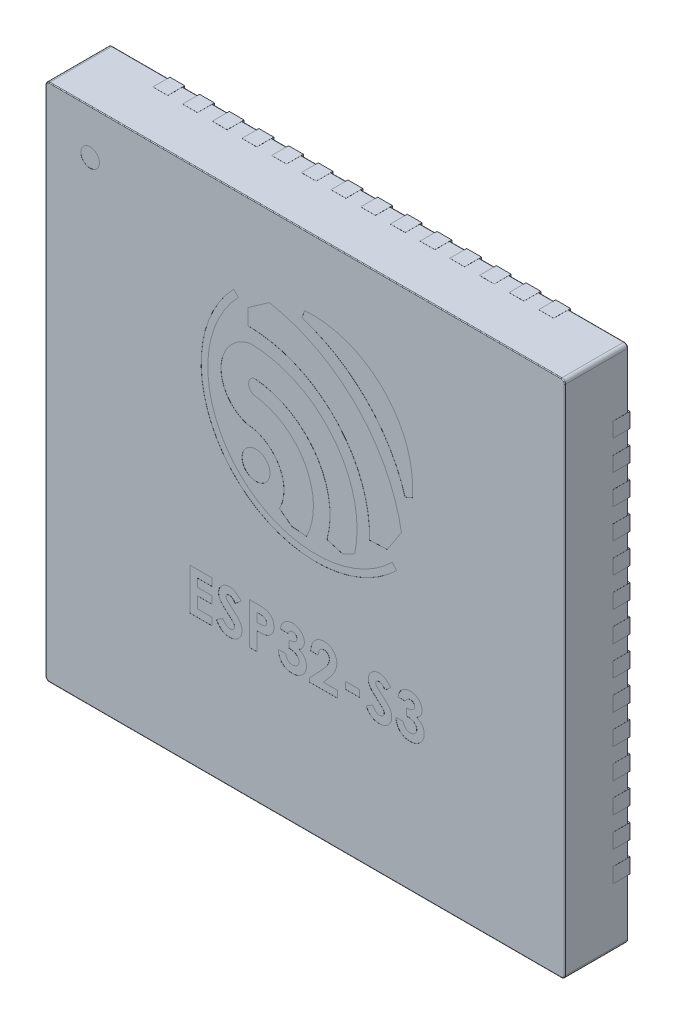
SolidWorks part; units mm, degrees
other "ESP32-S3-SoC" parameters "D5"=0.3678, "D1"=3.1308, "D2"=3.0402, "D3"=0.4115, "D4"=0.3, "D6"=0.3296, "D7"=0.2637, "D8"=0.9806, "D10"=0.4, "D11"=0.25, "D9"=7
ref_plane "Front Plane" through (0, 0, 0) normal (0, 0, 1) x (1, 0, 0)
ref_plane "Top Plane" through (0, 0, 0) normal (0, 1, 0) x (1, 0, 0)
ref_plane "Right Plane" through (0, 0, 0) normal (1, 0, 0) x (0, 0, -1)
sketch "Sketch1" plane through (0, 0, 0) normal (0, 1, 0) x (1, 0, 0)
  line L1 (-3.5, -3.5) -> (3.5, -3.5)
  line L2 (-3.5, -3.5) -> (-3.5, 3.5)
  line L3 (-3.5, 3.5) -> (3.5, 3.5)
  line L4 (3.5, -3.5) -> (3.5, 3.5)
  line L5 (-3.5, -3.5) -> (3.5, 3.5) construction
  line L6 (-3.5, 3.5) -> (3.5, -3.5) construction
  point P0 (0, 0)
  dimension "D1" = 7
  dimension "D2" = 7
extrude "Boss-Extrude1" add sketch "Sketch1" along normal blind 0.85
fillet "Fillet1" radius 0.05 4 edges at (3.5, 0.425, -3.5) (3.5, 0.425, 3.5) (-3.5, 0.425, 3.5) (-3.5, 0.425, -3.5)
fillet "Fillet2" radius 0.01 16 edges at (3.4854, 0.85, 3.4854) (0, 0.85, 3.5) (-3.4854, 0.85, 3.4854) (-3.5, 0.85, 0) (-3.4854, 0.85, -3.4854) (0, 0.85, -3.5) (3.4854, 0.85, -3.4854) (3.5, 0.85, 0) (3.5, 0, 0) (3.4854, 0, -3.4854) (0, 0, -3.5) (3.4854, 0, 3.4854) (0, 0, 3.5) (-3.4854, 0, 3.4854) (-3.5, 0, 0) (-3.4854, 0, -3.4854)
sketch "Sketch2" plane through (0, 0, 0) normal (0, -1, 0) x (1, 0, 0)
  line L0 (1.5, 2) -> (2, 1.5)
  line L1 (-1.875, -2) -> (1.875, -2)
  line L2 (-2, -1.875) -> (-2, 1.875)
  line L3 (-1.875, 2) -> (1.5, 2)
  line L4 (2, -1.875) -> (2, 1.5)
  line L5 (-1.9634, -1.9634) -> (2, 2) construction
  line L6 (-1.9634, 1.9634) -> (1.9634, -1.9634) construction
  line L7 (1.5, 2) -> (2, 2) construction
  line L8 (2, 1.5) -> (2, 2) construction
  line L9 (-2, 2) -> (-1.875, 2) construction
  line L10 (-2, 2) -> (-1.9634, 1.9634) construction
  line L11 (-2, 1.875) -> (-2, 2) construction
  line L12 (-2, -2) -> (-2, -1.875) construction
  line L13 (-2, -2) -> (-1.9634, -1.9634) construction
  line L14 (-2, -2) -> (-1.875, -2) construction
  line L15 (2, -2) -> (2, -1.875) construction
  line L16 (1.9634, -1.9634) -> (2, -2) construction
  line L17 (1.875, -2) -> (2, -2) construction
  line L18 (-1.9, 3.501) -> (-1.9, 3.101)
  line L23 (-0.3, 3.501) -> (-0.1, 3.501)
  line L24 (-0.3, 3.501) -> (-0.3, 3.101)
  line L25 (-0.3, 3.101) -> (-0.1, 3.101)
  line L26 (-0.1, 3.501) -> (-0.1, 3.101)
  line L27 (-0.3, 3.501) -> (-0.1, 3.101) construction
  line L28 (-0.3, 3.101) -> (-0.1, 3.501) construction
  line L30 (-0.7, 3.501) -> (-0.7, 3.101)
  line L31 (-0.7, 3.501) -> (-0.5, 3.501)
  line L32 (-0.5, 3.501) -> (-0.5, 3.101)
  line L33 (-0.7, 3.101) -> (-0.5, 3.101)
  line L34 (-0.7, 3.101) -> (-0.5, 3.501) construction
  line L35 (-0.7, 3.501) -> (-0.5, 3.101) construction
  line L36 (-1.1, 3.501) -> (-1.1, 3.101)
  line L37 (-1.1, 3.501) -> (-0.9, 3.501)
  line L38 (-0.9, 3.501) -> (-0.9, 3.101)
  line L39 (-1.1, 3.101) -> (-0.9, 3.101)
  line L40 (-1.1, 3.101) -> (-0.9, 3.501) construction
  line L41 (-1.1, 3.501) -> (-0.9, 3.101) construction
  line L42 (-1.5, 3.501) -> (-1.5, 3.101)
  line L43 (-1.5, 3.501) -> (-1.3, 3.501)
  line L44 (-1.3, 3.501) -> (-1.3, 3.101)
  line L45 (-1.5, 3.101) -> (-1.3, 3.101)
  line L46 (-1.5, 3.101) -> (-1.3, 3.501) construction
  line L47 (-1.5, 3.501) -> (-1.3, 3.101) construction
  line L48 (-0.3, 3.501) -> (-0.7, 3.501) construction
  line L49 (0, 0.0183) -> (0, 4.8642) construction
  line L66 (0, -1000) -> (0, 49000) construction
  line L162 (-1.9, 3.501) -> (-1.7, 3.501)
  line L163 (-3.5, 3.5) -> (3.5, 3.5) construction
  line L164 (-1.7, 3.501) -> (-1.7, 3.101)
  line L165 (-1.9, 3.101) -> (-1.7, 3.101)
  line L166 (-1.9, 3.101) -> (-1.7, 3.501) construction
  line L167 (-1.9, 3.501) -> (-1.7, 3.101) construction
  line L168 (-2.3, 3.501) -> (-2.3, 3.101)
  line L169 (-2.3, 3.501) -> (-2.1, 3.501)
  line L170 (-2.1, 3.501) -> (-2.1, 3.101)
  line L171 (-2.3, 3.101) -> (-2.1, 3.101)
  line L172 (-2.3, 3.101) -> (-2.1, 3.501) construction
  line L173 (-2.3, 3.501) -> (-2.1, 3.101) construction
  line L174 (-2.7, 3.501) -> (-2.7, 3.101)
  line L175 (-2.7, 3.501) -> (-2.5, 3.501)
  line L176 (-2.5, 3.501) -> (-2.5, 3.101)
  line L177 (-2.7, 3.101) -> (-2.5, 3.101)
  line L178 (-2.7, 3.101) -> (-2.5, 3.501) construction
  line L179 (-2.7, 3.501) -> (-2.5, 3.101) construction
  line L180 (-1000, 0) -> (49000, 0) construction
  line L181 (2.7, 3.501) -> (2.5, 3.101) construction
  line L182 (2.7, 3.101) -> (2.5, 3.501) construction
  line L183 (2.3, 3.501) -> (2.1, 3.101) construction
  line L184 (2.3, 3.101) -> (2.1, 3.501) construction
  line L185 (1.9, 3.501) -> (1.7, 3.101) construction
  line L186 (1.9, 3.101) -> (1.7, 3.501) construction
  line L187 (0.3, 3.501) -> (0.7, 3.501) construction
  line L188 (1.5, 3.501) -> (1.3, 3.101) construction
  line L189 (1.5, 3.101) -> (1.3, 3.501) construction
  line L190 (1.1, 3.501) -> (0.9, 3.101) construction
  line L191 (1.1, 3.101) -> (0.9, 3.501) construction
  line L192 (0.7, 3.501) -> (0.5, 3.101) construction
  line L193 (0.7, 3.101) -> (0.5, 3.501) construction
  line L194 (0.3, 3.101) -> (0.1, 3.501) construction
  line L195 (0.3, 3.501) -> (0.1, 3.101) construction
  line L196 (2.7, 3.101) -> (2.5, 3.101)
  line L197 (2.5, 3.501) -> (2.5, 3.101)
  line L198 (2.7, 3.501) -> (2.5, 3.501)
  line L199 (2.7, 3.501) -> (2.7, 3.101)
  line L200 (2.3, 3.101) -> (2.1, 3.101)
  line L201 (2.1, 3.501) -> (2.1, 3.101)
  line L202 (2.3, 3.501) -> (2.1, 3.501)
  line L203 (2.3, 3.501) -> (2.3, 3.101)
  line L204 (1.9, 3.101) -> (1.7, 3.101)
  line L205 (1.7, 3.501) -> (1.7, 3.101)
  line L206 (1.9, 3.501) -> (1.7, 3.501)
  line L207 (1.5, 3.101) -> (1.3, 3.101)
  line L208 (1.3, 3.501) -> (1.3, 3.101)
  line L209 (1.5, 3.501) -> (1.3, 3.501)
  line L210 (1.5, 3.501) -> (1.5, 3.101)
  line L211 (1.1, 3.101) -> (0.9, 3.101)
  line L212 (0.9, 3.501) -> (0.9, 3.101)
  line L213 (1.1, 3.501) -> (0.9, 3.501)
  line L214 (1.1, 3.501) -> (1.1, 3.101)
  line L215 (0.7, 3.101) -> (0.5, 3.101)
  line L216 (0.5, 3.501) -> (0.5, 3.101)
  line L217 (0.7, 3.501) -> (0.5, 3.501)
  line L218 (0.7, 3.501) -> (0.7, 3.101)
  line L219 (0.1, 3.501) -> (0.1, 3.101)
  line L220 (0.3, 3.101) -> (0.1, 3.101)
  line L221 (0.3, 3.501) -> (0.3, 3.101)
  line L222 (0.3, 3.501) -> (0.1, 3.501)
  line L223 (1.9, 3.501) -> (1.9, 3.101)
  line L224 (0.3, -3.501) -> (0.1, -3.101) construction
  line L225 (0.3, -3.101) -> (0.1, -3.501) construction
  line L226 (0.7, -3.101) -> (0.5, -3.501) construction
  line L227 (0.7, -3.501) -> (0.5, -3.101) construction
  line L228 (1.1, -3.101) -> (0.9, -3.501) construction
  line L229 (1.1, -3.501) -> (0.9, -3.101) construction
  line L230 (1.5, -3.101) -> (1.3, -3.501) construction
  line L231 (1.5, -3.501) -> (1.3, -3.101) construction
  line L232 (0.3, -3.501) -> (0.7, -3.501) construction
  line L233 (1.9, -3.101) -> (1.7, -3.501) construction
  line L234 (1.9, -3.501) -> (1.7, -3.101) construction
  line L235 (2.3, -3.101) -> (2.1, -3.501) construction
  line L236 (2.3, -3.501) -> (2.1, -3.101) construction
  line L237 (2.7, -3.101) -> (2.5, -3.501) construction
  line L238 (2.7, -3.501) -> (2.5, -3.101) construction
  line L239 (-2.7, -3.501) -> (-2.5, -3.101) construction
  line L240 (-2.7, -3.101) -> (-2.5, -3.501) construction
  line L241 (-2.3, -3.501) -> (-2.1, -3.101) construction
  line L242 (-2.3, -3.101) -> (-2.1, -3.501) construction
  line L243 (-1.9, -3.501) -> (-1.7, -3.101) construction
  line L244 (-1.9, -3.101) -> (-1.7, -3.501) construction
  line L245 (-0.3, -3.501) -> (-0.7, -3.501) construction
  line L246 (-1.5, -3.501) -> (-1.3, -3.101) construction
  line L247 (-1.5, -3.101) -> (-1.3, -3.501) construction
  line L248 (-1.1, -3.501) -> (-0.9, -3.101) construction
  line L249 (-1.1, -3.101) -> (-0.9, -3.501) construction
  line L250 (-0.7, -3.501) -> (-0.5, -3.101) construction
  line L251 (-0.7, -3.101) -> (-0.5, -3.501) construction
  line L252 (-0.3, -3.101) -> (-0.1, -3.501) construction
  line L253 (-0.3, -3.501) -> (-0.1, -3.101) construction
  line L254 (1.9, -3.501) -> (1.9, -3.101)
  line L255 (0.3, -3.501) -> (0.1, -3.501)
  line L256 (0.3, -3.501) -> (0.3, -3.101)
  line L257 (0.3, -3.101) -> (0.1, -3.101)
  line L258 (0.1, -3.501) -> (0.1, -3.101)
  line L259 (0.7, -3.501) -> (0.7, -3.101)
  line L260 (0.7, -3.501) -> (0.5, -3.501)
  line L261 (0.5, -3.501) -> (0.5, -3.101)
  line L262 (0.7, -3.101) -> (0.5, -3.101)
  line L263 (1.1, -3.501) -> (1.1, -3.101)
  line L264 (1.1, -3.501) -> (0.9, -3.501)
  line L265 (0.9, -3.501) -> (0.9, -3.101)
  line L266 (1.1, -3.101) -> (0.9, -3.101)
  line L267 (1.5, -3.501) -> (1.5, -3.101)
  line L268 (1.5, -3.501) -> (1.3, -3.501)
  line L269 (1.3, -3.501) -> (1.3, -3.101)
  line L270 (1.5, -3.101) -> (1.3, -3.101)
  line L271 (1.9, -3.501) -> (1.7, -3.501)
  line L272 (1.7, -3.501) -> (1.7, -3.101)
  line L273 (1.9, -3.101) -> (1.7, -3.101)
  line L274 (2.3, -3.501) -> (2.3, -3.101)
  line L275 (2.3, -3.501) -> (2.1, -3.501)
  line L276 (2.1, -3.501) -> (2.1, -3.101)
  line L277 (2.3, -3.101) -> (2.1, -3.101)
  line L278 (2.7, -3.501) -> (2.7, -3.101)
  line L279 (2.7, -3.501) -> (2.5, -3.501)
  line L280 (2.5, -3.501) -> (2.5, -3.101)
  line L281 (2.7, -3.101) -> (2.5, -3.101)
  line L282 (-2.7, -3.101) -> (-2.5, -3.101)
  line L283 (-2.5, -3.501) -> (-2.5, -3.101)
  line L284 (-2.7, -3.501) -> (-2.5, -3.501)
  line L285 (-2.7, -3.501) -> (-2.7, -3.101)
  line L286 (-2.3, -3.101) -> (-2.1, -3.101)
  line L287 (-2.1, -3.501) -> (-2.1, -3.101)
  line L288 (-2.3, -3.501) -> (-2.1, -3.501)
  line L289 (-2.3, -3.501) -> (-2.3, -3.101)
  line L290 (-1.9, -3.101) -> (-1.7, -3.101)
  line L291 (-1.7, -3.501) -> (-1.7, -3.101)
  line L292 (-1.9, -3.501) -> (-1.7, -3.501)
  line L293 (-1.5, -3.101) -> (-1.3, -3.101)
  line L294 (-1.3, -3.501) -> (-1.3, -3.101)
  line L295 (-1.5, -3.501) -> (-1.3, -3.501)
  line L296 (-1.5, -3.501) -> (-1.5, -3.101)
  line L297 (-1.1, -3.101) -> (-0.9, -3.101)
  line L298 (-0.9, -3.501) -> (-0.9, -3.101)
  line L299 (-1.1, -3.501) -> (-0.9, -3.501)
  line L300 (-1.1, -3.501) -> (-1.1, -3.101)
  line L301 (-0.7, -3.101) -> (-0.5, -3.101)
  line L302 (-0.5, -3.501) -> (-0.5, -3.101)
  line L303 (-0.7, -3.501) -> (-0.5, -3.501)
  line L304 (-0.7, -3.501) -> (-0.7, -3.101)
  line L305 (-0.1, -3.501) -> (-0.1, -3.101)
  line L306 (-0.3, -3.101) -> (-0.1, -3.101)
  line L307 (-0.3, -3.501) -> (-0.3, -3.101)
  line L308 (-0.3, -3.501) -> (-0.1, -3.501)
  line L309 (-1.9, -3.501) -> (-1.9, -3.101)
  line L310 (3.501, 0.3) -> (3.101, 0.1) construction
  line L311 (3.101, 0.3) -> (3.501, 0.1) construction
  line L312 (3.101, 0.7) -> (3.501, 0.5) construction
  line L313 (3.501, 0.7) -> (3.101, 0.5) construction
  line L314 (3.101, 1.1) -> (3.501, 0.9) construction
  line L315 (3.501, 1.1) -> (3.101, 0.9) construction
  line L316 (3.101, 1.5) -> (3.501, 1.3) construction
  line L317 (3.501, 1.5) -> (3.101, 1.3) construction
  line L318 (3.501, 0.3) -> (3.501, 0.7) construction
  line L319 (3.101, 1.9) -> (3.501, 1.7) construction
  line L320 (3.501, 1.9) -> (3.101, 1.7) construction
  line L321 (3.101, 2.3) -> (3.501, 2.1) construction
  line L322 (3.501, 2.3) -> (3.101, 2.1) construction
  line L323 (3.101, 2.7) -> (3.501, 2.5) construction
  line L324 (3.501, 2.7) -> (3.101, 2.5) construction
  line L325 (3.501, -2.7) -> (3.101, -2.5) construction
  line L326 (3.101, -2.7) -> (3.501, -2.5) construction
  line L327 (3.501, -2.3) -> (3.101, -2.1) construction
  line L328 (3.101, -2.3) -> (3.501, -2.1) construction
  line L329 (3.501, -1.9) -> (3.101, -1.7) construction
  line L330 (3.101, -1.9) -> (3.501, -1.7) construction
  line L331 (3.501, -0.3) -> (3.501, -0.7) construction
  line L332 (3.501, -1.5) -> (3.101, -1.3) construction
  line L333 (3.101, -1.5) -> (3.501, -1.3) construction
  line L334 (3.501, -1.1) -> (3.101, -0.9) construction
  line L335 (3.101, -1.1) -> (3.501, -0.9) construction
  line L336 (3.501, -0.7) -> (3.101, -0.5) construction
  line L337 (3.101, -0.7) -> (3.501, -0.5) construction
  line L338 (3.101, -0.3) -> (3.501, -0.1) construction
  line L339 (3.501, -0.3) -> (3.101, -0.1) construction
  line L340 (3.501, 1.9) -> (3.101, 1.9)
  line L341 (3.501, 0.3) -> (3.501, 0.1)
  line L342 (3.501, 0.3) -> (3.101, 0.3)
  line L343 (3.101, 0.3) -> (3.101, 0.1)
  line L344 (3.501, 0.1) -> (3.101, 0.1)
  line L345 (3.501, 0.7) -> (3.101, 0.7)
  line L346 (3.501, 0.7) -> (3.501, 0.5)
  line L347 (3.501, 0.5) -> (3.101, 0.5)
  line L348 (3.101, 0.7) -> (3.101, 0.5)
  line L349 (3.501, 1.1) -> (3.101, 1.1)
  line L350 (3.501, 1.1) -> (3.501, 0.9)
  line L351 (3.501, 0.9) -> (3.101, 0.9)
  line L352 (3.101, 1.1) -> (3.101, 0.9)
  line L353 (3.501, 1.5) -> (3.101, 1.5)
  line L354 (3.501, 1.5) -> (3.501, 1.3)
  line L355 (3.501, 1.3) -> (3.101, 1.3)
  line L356 (3.101, 1.5) -> (3.101, 1.3)
  line L357 (3.501, 1.9) -> (3.501, 1.7)
  line L358 (3.501, 1.7) -> (3.101, 1.7)
  line L359 (3.101, 1.9) -> (3.101, 1.7)
  line L360 (3.501, 2.3) -> (3.101, 2.3)
  line L361 (3.501, 2.3) -> (3.501, 2.1)
  line L362 (3.501, 2.1) -> (3.101, 2.1)
  line L363 (3.101, 2.3) -> (3.101, 2.1)
  line L364 (3.501, 2.7) -> (3.101, 2.7)
  line L365 (3.501, 2.7) -> (3.501, 2.5)
  line L366 (3.501, 2.5) -> (3.101, 2.5)
  line L367 (3.101, 2.7) -> (3.101, 2.5)
  line L368 (3.101, -2.7) -> (3.101, -2.5)
  line L369 (3.501, -2.5) -> (3.101, -2.5)
  line L370 (3.501, -2.7) -> (3.501, -2.5)
  line L371 (3.501, -2.7) -> (3.101, -2.7)
  line L372 (3.101, -2.3) -> (3.101, -2.1)
  line L373 (3.501, -2.1) -> (3.101, -2.1)
  line L374 (3.501, -2.3) -> (3.501, -2.1)
  line L375 (3.501, -2.3) -> (3.101, -2.3)
  line L376 (3.101, -1.9) -> (3.101, -1.7)
  line L377 (3.501, -1.7) -> (3.101, -1.7)
  line L378 (3.501, -1.9) -> (3.501, -1.7)
  line L379 (3.101, -1.5) -> (3.101, -1.3)
  line L380 (3.501, -1.3) -> (3.101, -1.3)
  line L381 (3.501, -1.5) -> (3.501, -1.3)
  line L382 (3.501, -1.5) -> (3.101, -1.5)
  line L383 (3.101, -1.1) -> (3.101, -0.9)
  line L384 (3.501, -0.9) -> (3.101, -0.9)
  line L385 (3.501, -1.1) -> (3.501, -0.9)
  line L386 (3.501, -1.1) -> (3.101, -1.1)
  line L387 (3.101, -0.7) -> (3.101, -0.5)
  line L388 (3.501, -0.5) -> (3.101, -0.5)
  line L389 (3.501, -0.7) -> (3.501, -0.5)
  line L390 (3.501, -0.7) -> (3.101, -0.7)
  line L391 (3.501, -0.1) -> (3.101, -0.1)
  line L392 (3.101, -0.3) -> (3.101, -0.1)
  line L393 (3.501, -0.3) -> (3.101, -0.3)
  line L394 (3.501, -0.3) -> (3.501, -0.1)
  line L395 (3.501, -1.9) -> (3.101, -1.9)
  line L396 (-3.501, -0.3) -> (-3.101, -0.1) construction
  line L397 (-3.101, -0.3) -> (-3.501, -0.1) construction
  line L398 (-3.101, -0.7) -> (-3.501, -0.5) construction
  line L399 (-3.501, -0.7) -> (-3.101, -0.5) construction
  line L400 (-3.101, -1.1) -> (-3.501, -0.9) construction
  line L401 (-3.501, -1.1) -> (-3.101, -0.9) construction
  line L402 (-3.101, -1.5) -> (-3.501, -1.3) construction
  line L403 (-3.501, -1.5) -> (-3.101, -1.3) construction
  line L404 (-3.501, -0.3) -> (-3.501, -0.7) construction
  line L405 (-3.101, -1.9) -> (-3.501, -1.7) construction
  line L406 (-3.501, -1.9) -> (-3.101, -1.7) construction
  line L407 (-3.101, -2.3) -> (-3.501, -2.1) construction
  line L408 (-3.501, -2.3) -> (-3.101, -2.1) construction
  line L409 (-3.101, -2.7) -> (-3.501, -2.5) construction
  line L410 (-3.501, -2.7) -> (-3.101, -2.5) construction
  line L411 (-3.501, 2.7) -> (-3.101, 2.5) construction
  line L412 (-3.101, 2.7) -> (-3.501, 2.5) construction
  line L413 (-3.501, 2.3) -> (-3.101, 2.1) construction
  line L414 (-3.101, 2.3) -> (-3.501, 2.1) construction
  line L415 (-3.501, 1.9) -> (-3.101, 1.7) construction
  line L416 (-3.101, 1.9) -> (-3.501, 1.7) construction
  line L417 (-3.501, 0.3) -> (-3.501, 0.7) construction
  line L418 (-3.501, 1.5) -> (-3.101, 1.3) construction
  line L419 (-3.101, 1.5) -> (-3.501, 1.3) construction
  line L420 (-3.501, 1.1) -> (-3.101, 0.9) construction
  line L421 (-3.101, 1.1) -> (-3.501, 0.9) construction
  line L422 (-3.501, 0.7) -> (-3.101, 0.5) construction
  line L423 (-3.101, 0.7) -> (-3.501, 0.5) construction
  line L424 (-3.101, 0.3) -> (-3.501, 0.1) construction
  line L425 (-3.501, 0.3) -> (-3.101, 0.1) construction
  line L426 (-3.501, -1.9) -> (-3.101, -1.9)
  line L427 (-3.501, -0.3) -> (-3.501, -0.1)
  line L428 (-3.501, -0.3) -> (-3.101, -0.3)
  line L429 (-3.101, -0.3) -> (-3.101, -0.1)
  line L430 (-3.501, -0.1) -> (-3.101, -0.1)
  line L431 (-3.501, -0.7) -> (-3.101, -0.7)
  line L432 (-3.501, -0.7) -> (-3.501, -0.5)
  line L433 (-3.501, -0.5) -> (-3.101, -0.5)
  line L434 (-3.101, -0.7) -> (-3.101, -0.5)
  line L435 (-3.501, -1.1) -> (-3.101, -1.1)
  line L436 (-3.501, -1.1) -> (-3.501, -0.9)
  line L437 (-3.501, -0.9) -> (-3.101, -0.9)
  line L438 (-3.101, -1.1) -> (-3.101, -0.9)
  line L439 (-3.501, -1.5) -> (-3.101, -1.5)
  line L440 (-3.501, -1.5) -> (-3.501, -1.3)
  line L441 (-3.501, -1.3) -> (-3.101, -1.3)
  line L442 (-3.101, -1.5) -> (-3.101, -1.3)
  line L443 (-3.501, -1.9) -> (-3.501, -1.7)
  line L444 (-3.501, -1.7) -> (-3.101, -1.7)
  line L445 (-3.101, -1.9) -> (-3.101, -1.7)
  line L446 (-3.501, -2.3) -> (-3.101, -2.3)
  line L447 (-3.501, -2.3) -> (-3.501, -2.1)
  line L448 (-3.501, -2.1) -> (-3.101, -2.1)
  line L449 (-3.101, -2.3) -> (-3.101, -2.1)
  line L450 (-3.501, -2.7) -> (-3.101, -2.7)
  line L451 (-3.501, -2.7) -> (-3.501, -2.5)
  line L452 (-3.501, -2.5) -> (-3.101, -2.5)
  line L453 (-3.101, -2.7) -> (-3.101, -2.5)
  line L454 (-3.101, 2.7) -> (-3.101, 2.5)
  line L455 (-3.501, 2.5) -> (-3.101, 2.5)
  line L456 (-3.501, 2.7) -> (-3.501, 2.5)
  line L457 (-3.501, 2.7) -> (-3.101, 2.7)
  line L458 (-3.101, 2.3) -> (-3.101, 2.1)
  line L459 (-3.501, 2.1) -> (-3.101, 2.1)
  line L460 (-3.501, 2.3) -> (-3.501, 2.1)
  line L461 (-3.501, 2.3) -> (-3.101, 2.3)
  line L462 (-3.101, 1.9) -> (-3.101, 1.7)
  line L463 (-3.501, 1.7) -> (-3.101, 1.7)
  line L464 (-3.501, 1.9) -> (-3.501, 1.7)
  line L465 (-3.101, 1.5) -> (-3.101, 1.3)
  line L466 (-3.501, 1.3) -> (-3.101, 1.3)
  line L467 (-3.501, 1.5) -> (-3.501, 1.3)
  line L468 (-3.501, 1.5) -> (-3.101, 1.5)
  line L469 (-3.101, 1.1) -> (-3.101, 0.9)
  line L470 (-3.501, 0.9) -> (-3.101, 0.9)
  line L471 (-3.501, 1.1) -> (-3.501, 0.9)
  line L472 (-3.501, 1.1) -> (-3.101, 1.1)
  line L473 (-3.101, 0.7) -> (-3.101, 0.5)
  line L474 (-3.501, 0.5) -> (-3.101, 0.5)
  line L475 (-3.501, 0.7) -> (-3.501, 0.5)
  line L476 (-3.501, 0.7) -> (-3.101, 0.7)
  line L477 (-3.501, 0.1) -> (-3.101, 0.1)
  line L478 (-3.101, 0.3) -> (-3.101, 0.1)
  line L479 (-3.501, 0.3) -> (-3.101, 0.3)
  line L480 (-3.501, 0.3) -> (-3.501, 0.1)
  line L481 (-3.501, 1.9) -> (-3.101, 1.9)
  arc A0 (-1.875, 2) -> (-2, 1.875) centre (-1.875, 1.875) ccw
  arc A1 (-2, -1.875) -> (-1.875, -2) centre (-1.875, -1.875) ccw
  arc A2 (1.875, -2) -> (2, -1.875) centre (1.875, -1.875) ccw
  point P0 (0, 0)
  point P12 (-0.2, 3.301)
  point P76 (0.2, 3.301)
  point P133 (0.2, -3.301)
  point P134 (-0.2, -3.301)
  point P201 (3.301, 0.2)
  point P202 (3.301, -0.2)
  point P259 (-3.301, -0.2)
  point P260 (-3.301, 0.2)
  dimension "D5" = 0.25
  dimension "D1" = 4
  dimension "D2" = 4
  dimension "D4" = 45
  dimension "D7" = 0.2
  dimension "D8" = 0.2
  dimension "D11" = 0.001
  dimension "D6" = 0.4
  dimension "D3" = 0.5
extrude "Boss-Extrude2" add sketch "Sketch2" along normal blind 0.025 and the other way blind 0.203
sketch "Sketch3" plane through (0, 0.85, 0) normal (0, 1, 0) x (1, 0, 0)
  line L7 (-3.5, 1.745) -> (3.49, 1.745) construction
  line L8 (-3.5, 3.5) -> (-3.5, -3.5) construction
  line L9 (3.5, 3.45) -> (3.5, -3.45) construction
  line L11 (3.49, -3.45) -> (3.49, 3.45) construction
  line L12 (3.45, -3.5) -> (-3.45, -3.5) construction
  line L13 (-1.3455, -1.0584) -> (-1.4421, -1.0995)
  line L14 (0.0091, -2.5583) -> (0.046, -2.4556)
  line L15 (-0.8654, -0.3165) -> (-1.1036, -0.3267)
  line L16 (-1.1036, -0.3267) -> (-1.2961, -0.6206)
  line L17 (0.4846, -2.4147) -> (0.7735, -2.212)
  line L18 (0.7735, -2.212) -> (0.7735, -1.999)
  line L19 (0.9001, -2.2687) -> (0.9674, -2.3282)
  line L20 (-1.2305, -0.1441) -> (-1.1706, -0.2111)
  line L21 (0.3479, -0.0784) -> (0.1821, 0.047)
  line L22 (0.1821, 0.047) -> (-0.0169, 0.0645)
  line L23 (-0.2915, -0.0371) -> (-0.5019, 0.0255)
  line L24 (-0.5019, 0.0255) -> (-0.6657, -0.0565)
  line L25 (0, 0) -> (0, 3.49) construction
  line L26 (3.45, 3.49) -> (-3.45, 3.49) construction
  circle A10 centre (2.9, -2.9) radius 0.125
  arc A11 (-1.3455, -1.0584) -> (0.046, -2.4556) centre (0.6641, -0.4486) ccw
  arc A12 (-1.2961, -0.6206) -> (0.4846, -2.4147) centre (0.8767, -0.2449) ccw
  arc A13 (0.7494, -1.8089) -> (0.7907, -0.8472) centre (0.6367, -1.3223) ccw
  arc A14 (0.9674, -2.3282) -> (-1.2305, -0.1441) centre (-0.1457, -1.2504) ccw
  circle A15 centre (0.6641, -0.4254) radius 0.1881
  arc A16 (-0.2915, -0.0371) -> (0.6891, -1.4288) centre (0.7584, -0.3386) ccw
  arc A17 (0.3479, -0.0784) -> (0.7907, -0.8472) centre (0.8131, -0.3223) ccw
  arc A18 (-0.0169, 0.0645) -> (0.6928, -1.2313) centre (0.793, -0.3342) ccw
  arc A19 (-0.6657, -0.0565) -> (0.7494, -1.8089) centre (0.7499, -0.3609) ccw
  arc A20 (0.9001, -2.2687) -> (-1.1706, -0.2111) centre (-0.1457, -1.2504) ccw
  arc A21 (-0.8654, -0.3165) -> (0.7735, -1.999) centre (0.7719, -0.3611) ccw
  arc A22 (0.6928, -1.2313) -> (0.6891, -1.4288) centre (0.6596, -1.3294) cw
  arc A23 (-1.4421, -1.0995) -> (0.0091, -2.5583) centre (-0.1022, -1.2178) ccw
  text T0 "ESP32-S3" font "Century Gothic" height 0.56
  point P0 (0, 1.745)
  point P54 (0, 0)
  dimension "D2" = 0.25
  dimension "D3" = 0.6
  dimension "D4" = 0.6
extrude "Cut-Extrude1" cut sketch "Sketch3" against normal blind 0.001
move or copy body "Body-Move/Copy1" bodies to move or copy 131 copy no rotation origin (0, 0, 0) rotation axis (0, 0.7071, 0.7071) rotation angle 180
move or copy body "Body-Move/Copy2" bodies to move or copy 132 copy no translate (0, 0, 0.025)
equation "\"D8@Sketch2\"=\"D10@Sketch2\"/2"
equation "\"D4@Sketch3\"=\"D3@Sketch3\""
